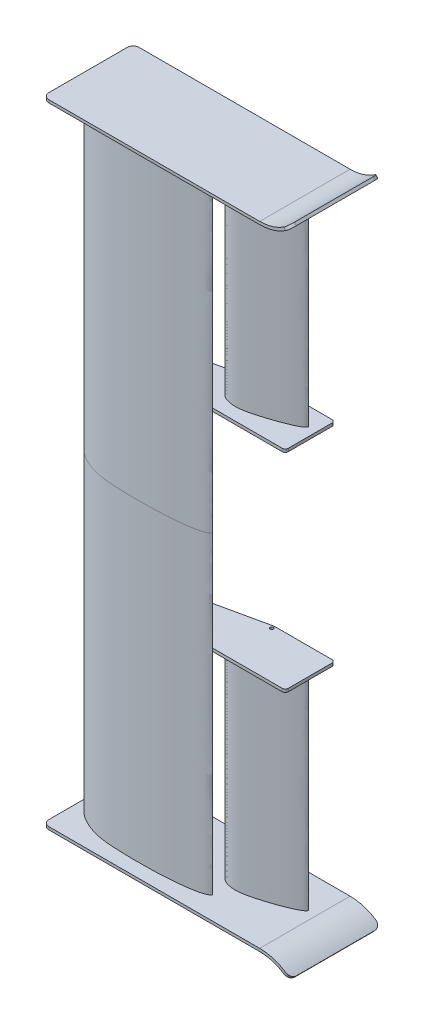
SolidWorks part; units mm, degrees
material "Pine"
ref_plane "Front Plane" through (0, 0, 0) normal (0, 0, 1) x (1, 0, 0)
ref_plane "Top Plane" through (0, 0, 0) normal (0, 1, 0) x (1, 0, 0)
ref_plane "Right Plane" through (0, 0, 0) normal (1, 0, 0) x (0, 0, -1)
curve "Curve1"
  spline degree 3 poles (-3.7953, 0, -0.0099) (-3.8135, 0, 0.0025) (-3.7975, 0, -0.0094) (-3.7869, 0, -0.0198) (-3.7634, 0, -0.0415) (-3.7356, 0, -0.0646) (-3.6977, 0, -0.0879) (-3.6505, 0, -0.1105) (-3.5935, 0, -0.134) (-3.5268, 0, -0.1582) (-3.4508, 0, -0.1829) (-3.3657, 0, -0.2079) (-3.2722, 0, -0.233) (-3.1706, 0, -0.258) (-3.0616, 0, -0.2828) (-2.9459, 0, -0.3071) (-2.8241, 0, -0.331) (-2.697, 0, -0.354) (-2.5653, 0, -0.3761) (-2.4298, 0, -0.3971) (-2.2915, 0, -0.417) (-2.1511, 0, -0.4356) (-2.0096, 0, -0.4529) (-1.8684, 0, -0.4689) (-1.7284, 0, -0.4834) (-1.5908, 0, -0.496) (-1.4567, 0, -0.506) (-1.3267, 0, -0.5129) (-1.2016, 0, -0.5159) (-1.082, 0, -0.5155) (-0.9682, 0, -0.5097) (-0.8601, 0, -0.4978) (-0.7573, 0, -0.4811) (-0.6597, 0, -0.4593) (-0.5675, 0, -0.4338) (-0.481, 0, -0.4051) (-0.4006, 0, -0.3736) (-0.3268, 0, -0.3398) (-0.2599, 0, -0.3041) (-0.2001, 0, -0.2671) (-0.148, 0, -0.2293) (-0.1034, 0, -0.1913) (-0.0671, 0, -0.1529) (-0.0392, 0, -0.1144) (-0.0186, 0, -0.0769) (-0.0054, 0, -0.0412) (0.0009, 0, -0.0084) (-0.0003, 0, 0.0194) (-0.0075, 0, 0.0449) (-0.0341, 0, 0.0576) (-0.0699, 0, 0.0593) (-0.1188, 0, 0.0611) (-0.1803, 0, 0.0584) (-0.2538, 0, 0.0535) (-0.3383, 0, 0.0457) (-0.433, 0, 0.0352) (-0.5376, 0, 0.0216) (-0.6518, 0, 0.0027) (-0.7763, 0, -0.0211) (-0.9117, 0, -0.0469) (-1.0573, 0, -0.0742) (-1.2123, 0, -0.1018) (-1.3754, 0, -0.1287) (-1.5454, 0, -0.154) (-1.7209, 0, -0.1767) (-1.9002, 0, -0.1962) (-2.0817, 0, -0.2116) (-2.2636, 0, -0.2225) (-2.4439, 0, -0.2285) (-2.6207, 0, -0.2293) (-2.792, 0, -0.2247) (-2.9559, 0, -0.215) (-3.1104, 0, -0.2002) (-3.2537, 0, -0.1809) (-3.3838, 0, -0.1577) (-3.4993, 0, -0.1313) (-3.598, 0, -0.103) (-3.6788, 0, -0.0729) (-3.7364, 0, -0.0453) (-3.7789, 0, -0.0198) (-3.7953, 0, -0.0099) (-3.8135, 0, 0.0025) (-3.7975, 0, -0.0094) knots -0.009748 -0.004147 -0.001 0 0.00098 0.003649 0.007483 0.012095 0.017526 0.024052 0.031783 0.040678 0.05071 0.061833 0.073989 0.087118 0.101145 0.115991 0.13157 0.147788 0.164551 0.181758 0.199312 0.217095 0.23499 0.252857 0.270541 0.287887 0.304773 0.321101 0.336806 0.3518 0.366031 0.379616 0.392653 0.40517 0.417172 0.428604 0.439419 0.449597 0.459102 0.467908 0.475988 0.483309 0.489875 0.495803 0.501149 0.505903 0.510047 0.513579 0.516447 0.51935 0.523823 0.529974 0.537716 0.546968 0.557637 0.56962 0.582804 0.597247 0.613135 0.630444 0.649056 0.668822 0.689595 0.71119 0.733427 0.756094 0.778989 0.80189 0.824567 0.846792 0.868338 0.888978 0.908492 0.926659 0.943286 0.958169 0.971136 0.981956 0.990252 0.995853 0.999 1 1.00098 1.003649 1.007483 periodic
sketch "Sketch1" plane through (0, 0, 0) normal (0, 1, 0) x (1, 0, 0)
  line L0 (310.4638, 47.2592) -> (12.7, 83.82) construction
  line L1 (1.9605, -3.6465) -> (6058.2865, 49321.1705) construction
  line L2 (-1184.907, 83.82) -> (48815.093, 83.82) construction
  spline S1 degree 3 poles (309.3965, 46.6419) (310.7573, 47.4184) (309.2169, 46.627) (307.8464, 46.0116) (304.2808, 44.4244) (299.5117, 42.8195) (292.9088, 41.2362) (284.923, 39.973) (275.6445, 39.0147) (265.2521, 38.4436) (253.8725, 38.3058) (241.6568, 38.6273) (228.7543, 39.4349) (215.3201, 40.7195) (201.5086, 42.4707) (187.4734, 44.6655) (173.3644, 47.2597) (159.3259, 50.2011) (145.4964, 53.4411) (131.9998, 56.8949) (118.9533, 60.4959) (106.4625, 64.1576) (94.6176, 67.7976) (83.4977, 71.3243) (73.1635, 74.6402) (63.6604, 77.6879) (54.9137, 80.2614) (46.8746, 82.3207) (39.5699, 84.0534) (33.038, 85.4728) (27.3449, 86.5566) (22.561, 87.3528) (18.7204, 87.6865) (15.9079, 87.89) (13.7076, 87.1554) (12.9043, 85.2313) (12.5434, 83.0703) (12.7206, 80.4413) (13.4119, 77.5319) (14.6633, 74.4034) (16.4744, 71.1235) (18.9449, 67.7742) (22.0646, 64.3831) (25.7789, 60.9242) (30.0938, 57.4603) (34.9849, 54.0342) (40.4276, 50.6811) (46.4099, 47.457) (52.8945, 44.3798) (59.859, 41.5056) (67.2773, 38.8735) (75.153, 36.5786) (83.4876, 34.6171) (92.3261, 33.0706) (101.6674, 31.9018) (111.4724, 30.9371) (121.6972, 30.2311) (132.2776, 29.7294) (143.1487, 29.3974) (154.2279, 29.189) (165.4237, 29.0939) (176.6407, 29.0916) (187.7917, 29.2025) (198.7968, 29.4317) (209.585, 29.7753) (220.0883, 30.245) (230.2446, 30.8257) (239.9912, 31.5224) (249.2694, 32.3192) (258.023, 33.213) (266.1996, 34.1979) (273.7521, 35.2653) (280.6378, 36.4021) (286.8184, 37.6037) (292.261, 38.8572) (296.9397, 40.1522) (300.8444, 41.4638) (304.0337, 42.9201) (306.4233, 44.4595) (308.4692, 45.931) (309.3965, 46.6419) (310.7573, 47.4184) (309.2169, 46.627) knots -0.007483 -0.003649 -0.00098 0 0.001 0.004147 0.009748 0.018044 0.028864 0.041831 0.056714 0.073341 0.091508 0.111022 0.131662 0.153208 0.175433 0.19811 0.221011 0.243906 0.266573 0.28881 0.310405 0.331178 0.350944 0.369556 0.386865 0.402753 0.417196 0.43038 0.442363 0.453032 0.462284 0.470026 0.476177 0.48065 0.483553 0.486421 0.489953 0.494097 0.498851 0.504197 0.510125 0.516691 0.524012 0.532092 0.540898 0.550403 0.560581 0.571396 0.582828 0.59483 0.607347 0.620384 0.633969 0.6482 0.663194 0.678899 0.695227 0.712113 0.729459 0.747143 0.76501 0.782905 0.800688 0.818242 0.835449 0.852212 0.86843 0.884009 0.898855 0.912882 0.926011 0.938167 0.94929 0.959322 0.968217 0.975948 0.982474 0.987905 0.992517 0.996351 0.99902 1 1.001 1.004147 1.009748 only from (310.4638, 47.2592) to (310.4638, 47.2592)
  dimension "D1" = 7
  dimension "D2" = 300
  dimension "D3" = 83.82
  dimension "D4" = 12.7
extrude "Main" add sketch "Sketch1" along normal blind 660.4
sketch "Sketch2" plane through (0, 660.4, 0) normal (0, 1, 0) x (1, 0, 0)
  line L1 (0, 0) -> (457.2, 0)
  line L2 (0, 0) -> (0, 190.5)
  line L3 (0, 190.5) -> (457.2, 190.5)
  line L4 (457.2, 0) -> (457.2, 190.5)
  line L5 (0, 0) -> (457.2, 190.5) construction
  line L6 (0, 190.5) -> (457.2, 0) construction
  point P4 (228.6, 95.25)
  dimension "D1" = 190.5
  dimension "D2" = 457.2
extrude "Endplate" add sketch "Sketch2" along normal blind 6 separate body
sketch "Sketch5" plane through (0, 0, -190.5) normal (0, 0, -1) x (-1, 0, 0)
  line L0 (-521.8516, 684.5445) -> (-517.9187, 689.0758)
  line L1 (-457.2, 666.4) -> (-457.2, 660.4) construction
  line L2 (-457.2, 666.4) -> (-457.2, 660.4)
  line L3 (-457.2, 666.4) -> (0, 666.4) construction
  arc A0 (-457.2, 666.4) -> (-517.9187, 689.0758) centre (-457.2, 759.0309) cw
  arc A1 (-457.2, 660.4) -> (-521.8516, 684.5445) centre (-457.2, 759.0309) cw
extrude "Boss-Extrude5" add sketch "Sketch5" against normal up to surface (190.5 mm away) up to face at (228.6, 663.4, 0)
sketch "Sketch3" plane through (0, 660.4, 0) normal (0, 1, 0) x (1, 0, 0)
  line L0 (439.8212, 120.0272) -> (292.1, 93.98) construction
  line L1 (275.4183, 188.5865) -> (-6915.6864, 40971.3682) construction
  line L2 (-1185.6674, 93.98) -> (48814.3326, 93.98) construction
  line L5 (0, 0) -> (457.2, 0) construction
  line L6 (0, 190.5) -> (0, 0) construction
  spline S1 degree 3 poles (439.4011, 119.576) (439.9382, 120.1462) (439.3173, 119.5427) (438.752, 119.0481) (437.2791, 117.7679) (435.2334, 116.3033) (432.3077, 114.581) (428.6739, 112.8096) (424.3774, 110.995) (419.4918, 109.2027) (414.0707, 107.4733) (408.1828, 105.8412) (401.8953, 104.3412) (395.2839, 102.9916) (388.4239, 101.8099) (381.3922, 100.8076) (374.2667, 99.9855) (367.1241, 99.3397) (360.0379, 98.8672) (353.0796, 98.5457) (346.3149, 98.3603) (339.8071, 98.2851) (333.6113, 98.2941) (327.7788, 98.3548) (322.3527, 98.4296) (317.3632, 98.4976) (312.8048, 98.4495) (308.6598, 98.259) (304.9138, 98.0196) (301.5831, 97.7434) (298.7024, 97.4294) (296.2986, 97.1108) (294.4134, 96.7089) (293.0389, 96.395) (292.0942, 95.7222) (291.9914, 94.6847) (292.1347, 93.5986) (292.6038, 92.3675) (293.3596, 91.0774) (294.4153, 89.7645) (295.7608, 88.4609) (297.4317, 87.2206) (299.4191, 86.0552) (301.7007, 84.9443) (304.2703, 83.9188) (307.1098, 82.9956) (310.2024, 82.1879) (313.5342, 81.5209) (317.0847, 80.9974) (320.835, 80.6413) (324.7668, 80.4672) (328.8681, 80.5212) (333.14, 80.8017) (337.5923, 81.3543) (342.2297, 82.161) (347.059, 83.133) (352.0512, 84.2902) (357.1836, 85.597) (362.4301, 87.0275) (367.7582, 88.5474) (373.1254, 90.1386) (378.4892, 91.7773) (383.8048, 93.4605) (389.0334, 95.1788) (394.1416, 96.9202) (399.0951, 98.6802) (403.8665, 100.4426) (408.425, 102.2006) (412.7449, 103.9379) (416.7998, 105.6449) (420.5655, 107.3111) (424.0207, 108.9256) (427.1469, 110.4757) (429.9265, 111.9538) (432.3457, 113.3488) (434.3935, 114.6519) (436.0688, 115.8499) (437.3809, 117.0125) (438.2984, 118.0979) (439.0616, 119.1006) (439.4011, 119.576) (439.9382, 120.1462) (439.3173, 119.5427) knots -0.007483 -0.003649 -0.00098 0 0.001 0.004147 0.009748 0.018044 0.028864 0.041831 0.056714 0.073341 0.091508 0.111022 0.131662 0.153208 0.175433 0.19811 0.221011 0.243906 0.266573 0.28881 0.310405 0.331178 0.350944 0.369556 0.386865 0.402753 0.417196 0.43038 0.442363 0.453032 0.462284 0.470026 0.476177 0.48065 0.483553 0.486421 0.489953 0.494097 0.498851 0.504197 0.510125 0.516691 0.524012 0.532092 0.540898 0.550403 0.560581 0.571396 0.582828 0.59483 0.607347 0.620384 0.633969 0.6482 0.663194 0.678899 0.695227 0.712113 0.729459 0.747143 0.76501 0.782905 0.800688 0.818242 0.835449 0.852212 0.86843 0.884009 0.898855 0.912882 0.926011 0.938167 0.94929 0.959322 0.968217 0.975948 0.982474 0.987905 0.992517 0.996351 0.99902 1 1.001 1.004147 1.009748 only from (439.8212, 120.0272) to (439.8212, 120.0272)
  dimension "D1" = 150
  dimension "D2" = 10
  dimension "D3" = 93.98
  dimension "D4" = 292.1
extrude "Second" add sketch "Sketch3" against normal blind 438.15 separate body
fillet "Fillet1" radius 12.7 4 edges at (519.8852, 686.8101, -190.5) (519.8852, 686.8101, 0) (0, 663.4, 0) (0, 663.4, -190.5)
sketch "Reference Sketch" plane through (0, 222.25, 0) normal (0, -1, 0) x (1, 0, 0)
  line L8 (310.4638, -47.2592) -> (12.7, -83.82) construction
  line L9 (310.4638, -47.2592) -> (12.7, -83.82) construction
  line L10 (50.516, -79.1768) -> (52.0637, -91.7821) construction
  line L11 (163.964, -65.2471) -> (163.3449, -60.205) construction
  line L14 (439.8212, -120.0272) -> (292.1, -93.98) construction
  line L15 (439.8212, -120.0272) -> (292.1, -93.98) construction
  line L17 (305.4892, -91.1825) -> (304.6071, -96.1853) construction
  line L18 (331.3854, -90.5903) -> (329.6212, -100.596) construction
  line L19 (356.8406, -92.4996) -> (354.6353, -105.0067) construction
  line L29 (330.2, -292.1) -> (330.2, -152.4) construction
  circle A0 centre (163.3449, -60.205) radius 3.302
  circle A1 centre (52.0637, -91.7821) radius 3.302
  circle A2 centre (52.0637, -91.7821) radius 6.35 construction
  circle A3 centre (163.3449, -60.205) radius 6.35 construction
  circle A7 centre (305.4892, -91.1825) radius 3.302 construction
  circle A8 centre (331.3854, -90.5903) radius 3.302 construction
  circle A9 centre (356.8406, -92.4996) radius 3.302 construction
  circle A10 centre (330.2, -292.1) radius 3.302
  circle A11 centre (330.2, -152.4) radius 3.302
  circle A12 centre (330.2, -292.1) radius 6.35 construction
  circle A13 centre (330.2, -152.4) radius 6.35 construction
  dimension "D5" = 6.604
  dimension "D6" = 12.7
  dimension "D7" = 6.604
  dimension "D14" = 6.604
  dimension "D1" = 38.1
  dimension "D2" = 12.7
  dimension "D3" = 152.4
  dimension "D4" = 5.08
  dimension "D8" = 5.08
  dimension "D9" = 10.16
  dimension "D10" = 12.7
  dimension "D11" = 12.7
  dimension "D12" = 38.1
  dimension "D13" = 63.5
  dimension "D16" = 139.7
  dimension "D17" = 330.2
  dimension "D18" = 152.4
sketch "Sketch23" plane through (0, 222.25, 0) normal (0, -1, 0) x (1, 0, 0)
  line L0 (328.8478, -158.6044) -> (50.7116, -97.9865)
  line L1 (50.3303, -85.6733) -> (161.6115, -54.0962)
  line L2 (330.2, -158.75) -> (450.85, -158.75)
  line L3 (457.2, -152.4) -> (457.2, -60.205)
  line L4 (450.85, -53.855) -> (163.3449, -53.855)
  line L5 (457.2, 0) -> (457.2, -190.5) construction
  circle A0 centre (52.0637, -91.7821) radius 6.35 construction
  circle A1 centre (330.2, -152.4) radius 6.35 construction
  circle A2 centre (163.3449, -60.205) radius 6.35 construction
  circle A3 centre (52.0637, -91.7821) radius 6.35 construction
  circle A4 centre (450.85, -152.4) radius 6.35 construction
  circle A5 centre (450.85, -60.205) radius 6.35 construction
  circle A6 centre (330.2, -152.4) radius 3.302 construction
  circle A7 centre (330.2, -152.4) radius 3.302
  circle A8 centre (52.0637, -91.7821) radius 3.302 construction
  circle A9 centre (52.0637, -91.7821) radius 3.302
  circle A10 centre (163.3449, -60.205) radius 3.302 construction
  circle A11 centre (163.3449, -60.205) radius 3.302
  arc A12 (163.3449, -53.855) -> (161.6115, -54.0962) centre (163.3449, -60.205) ccw
  arc A13 (50.7116, -97.9865) -> (50.3303, -85.6733) centre (52.0637, -91.7821) cw
  arc A14 (330.2, -158.75) -> (328.8478, -158.6044) centre (330.2, -152.4) cw
  arc A15 (450.85, -158.75) -> (457.2, -152.4) centre (450.85, -152.4) ccw
  arc A16 (457.2, -60.205) -> (450.85, -53.855) centre (450.85, -60.205) ccw
extrude "Inner Endplate" add sketch "Sketch23" along normal blind 6.35
ref_plane "Plane1" through (0, 215.9, 0) normal (0, -1, 0) x (-1, 0, 0)
sketch "Sketch8" [suppressed] plane through (0, 215.9, 0) normal (0, -1, 0) x (1, 0, 0)
  line L0 (48.3527, -96.9348) -> (326.4889, -297.2527)
  line L3 (336.55, -292.1) -> (336.55, -152.4)
  line L6 (166.416, -54.647) -> (333.271, -146.842)
  line L9 (161.6115, -54.0962) -> (50.3303, -85.6733)
  circle A7 centre (163.3449, -60.205) radius 6.35 construction
  circle A22 centre (52.0637, -91.7821) radius 6.35 construction
  circle A23 centre (330.2, -152.4) radius 6.35 construction
  circle A24 centre (330.2, -292.1) radius 6.35 construction
  arc A26 (326.4889, -297.2527) -> (336.55, -292.1) centre (330.2, -292.1) ccw
  arc A27 (333.271, -146.842) -> (336.55, -152.4) centre (330.2, -152.4) cw
  arc A28 (50.3303, -85.6733) -> (48.3527, -96.9348) centre (52.0637, -91.7821) ccw
  arc A29 (161.6115, -54.0962) -> (166.416, -54.647) centre (163.3449, -60.205) cw
  circle A30 centre (163.3449, -60.205) radius 6.35 construction
extrude "Bracket" [suppressed] add sketch "Sketch8" along normal blind 6.35 separate body
sketch "Sketch9" [suppressed] plane through (0, 215.9, 0) normal (0, -1, 0) x (1, 0, 0)
  circle A0 centre (52.0637, -91.7821) radius 3.302
  circle A1 centre (163.3449, -60.205) radius 3.302
  circle A2 centre (330.2, -152.4) radius 3.302
  circle A3 centre (330.2, -292.1) radius 3.302
  circle A8 centre (330.2, -152.4) radius 6.35 construction
  circle A9 centre (330.2, -292.1) radius 6.35 construction
  circle A10 centre (52.0637, -91.7821) radius 6.35 construction
  circle A11 centre (163.3449, -60.205) radius 6.35 construction
  dimension "D1" = 6.604
extrude "Cut-Extrude1" [suppressed] cut sketch "Sketch9" against normal through all both and the other way through all
sketch "Sketch15" [suppressed] plane through (0, 666.4, 0) normal (0, 1, 0) x (1, 0, 0)
  line L0 (310.4638, 47.2592) -> (12.7, 83.82) construction
  line L1 (310.4638, 47.2592) -> (12.7, 83.82) construction
  line L2 (439.8212, 120.0272) -> (292.1, 93.98) construction
  line L3 (439.8212, 120.0272) -> (292.1, 93.98) construction
  line L4 (24.6862, 77.2301) -> (25.3053, 82.2723) construction
  line L5 (73.4051, 57.1733) -> (75.7267, 76.0813) construction
  line L6 (123.0525, 44.6797) -> (126.148, 69.8903) construction
  line L7 (179.7766, 37.7148) -> (182.872, 62.9255) construction
  circle A0 centre (24.6862, 77.2301) radius 3.302
  circle A1 centre (73.4051, 57.1733) radius 3.302
  circle A2 centre (123.0525, 44.6797) radius 3.302
  circle A3 centre (179.7766, 37.7148) radius 3.302
  circle A9 centre (356.8406, 92.4996) radius 3.302 construction
  circle A12 centre (331.3854, 90.5903) radius 3.302 construction
  circle A14 centre (305.4892, 91.1825) radius 3.302 construction
  circle A15 centre (356.8406, 92.4996) radius 3.302
  circle A16 centre (331.3854, 90.5903) radius 3.302
  circle A17 centre (305.4892, 91.1825) radius 3.302
  dimension "D1" = 6.604
  dimension "D2" = 5.08
  dimension "D3" = 19.05
  dimension "D4" = 25.4
  dimension "D5" = 25.4
  dimension "D6" = 12.7
  dimension "D7" = 63.5
  dimension "D8" = 114.3
  dimension "D9" = 171.45
extrude "Cut-Extrude3" [suppressed] cut sketch "Sketch15" against normal up to surface and the other way through all
mirror "Mirror1" about plane through (13.6759, 0, -76.9872) normal (0, -1, 0) of bodies 105 134 101 103 126
ref_axis "Axis1" through (0, 660.4, 0) along (0, -1, 0)
